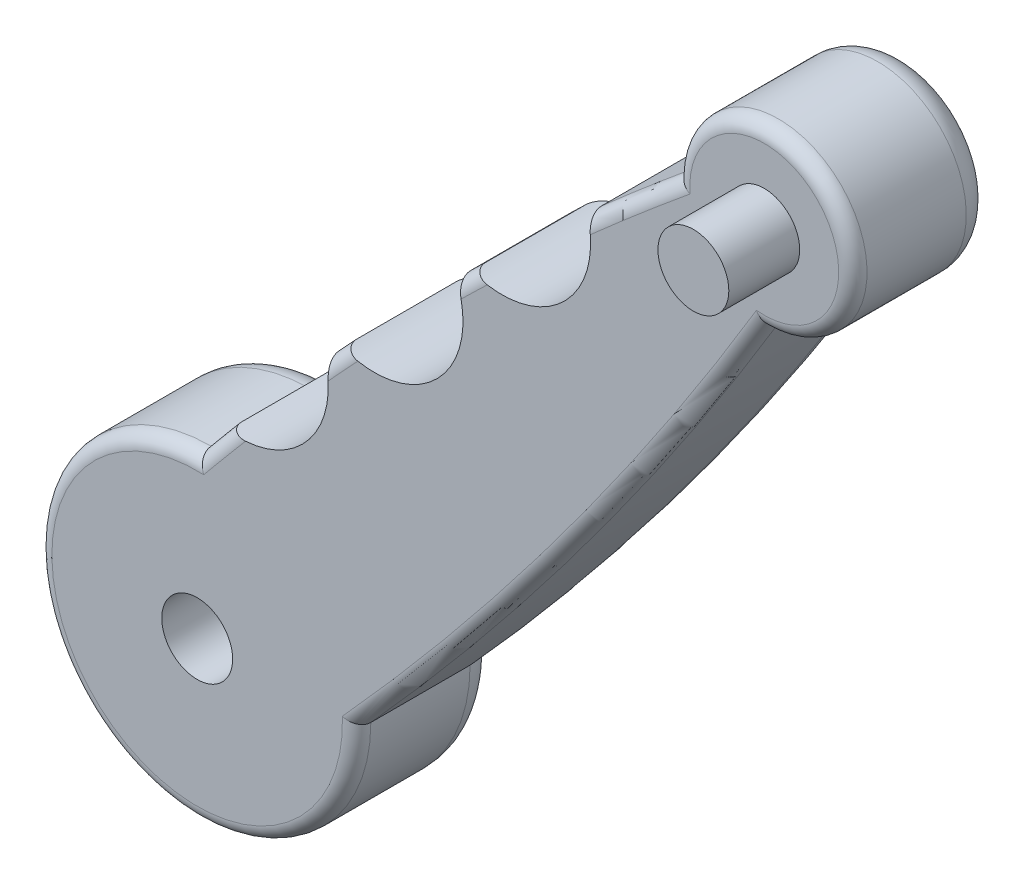
SolidWorks part; units mm, degrees
ref_plane "Front Plane" through (0, 0, 0) normal (0, 0, 1) x (1, 0, 0)
ref_plane "Top Plane" through (0, 0, 0) normal (0, 1, 0) x (1, 0, 0)
ref_plane "Right Plane" through (0, 0, 0) normal (1, 0, 0) x (0, 0, -1)
sketch "Sketch1" plane through (0, 0, 0) normal (0, 0, 1) x (1, 0, 0)
  arc A0 (0, 22.5) -> (22.5, 0) centre (0, 0) ccw
  arc A1 (80, 77.5) -> (67.5, 90) centre (80, 90) ccw
  arc A2 (0, 22.5) -> (67.5, 90) centre (385.6888, -295.6888) cw
  arc A3 (22.5, 0) -> (80, 77.5) centre (-348.4249, 335.283) ccw
  dimension "D1" = 45
  dimension "D2" = 25
  dimension "D3" = 90
  dimension "D5" = 500
  dimension "D6" = 500
  dimension "D4" = 80
extrude "Boss-Extrude1" add sketch "Sketch1" along normal mid plane 20 contours A2 A1 A3 A0
fillet "Fillet1" radius 2 4 edges at (53.1241, 37.3595, 10) (88.8388, 98.8388, 10) (32.1354, 57.8646, 10) (-15.9099, -15.9099, 10)
sketch "Sketch2" plane through (0, 0, 10) normal (0, 0, 1) x (1, 0, 0)
  circle A0 centre (0, 0) radius 5
  circle A1 centre (80, 90) radius 5
  dimension "D1" = 10
  dimension "D2" = 10
extrude "Boss-Extrude2" add sketch "Sketch2" along normal blind 10 contours A1
extrude "Cut-Extrude1" cut sketch "Sketch2<3>" against normal blind 10 contours A0
sketch "Sketch2<3>" plane through (0, 0, 10) normal (0, 0, 1) x (1, 0, 0) same geometry as "Sketch2"
fillet "Fillet2" radius 4 4 edges at (-15.9099, -15.9099, -10) (32.1354, 57.8646, -10) (53.1241, 37.3595, -10) (88.8388, 98.8388, -10)
sketch "Sketch3" plane through (0, 0, -10) normal (0, 0, -1) x (-1, 0, 0)
  circle A0 centre (0, 0) radius 12.5
  dimension "D1" = 25
extrude "Boss-Extrude3" add sketch "Sketch3" along normal blind 5
fillet "Fillet3" radius 5 1 edges at (-12.5, 0, -15)
sketch "Sketch4" plane through (0, 0, -15) normal (0, 0, -1) x (-1, 0, 0)
  line L0 (0, 0) -> (0, 12.5) construction
  circle A0 centre (0, 0) radius 12.5 construction
  circle A1 centre (0, 12.5) radius 2.5
  dimension "D1" = 5
extrude "Cut-Extrude2" cut sketch "Sketch4" against normal up to surface (5 mm away) up to face at (12.5, 0, -10)
pattern_circular "CirPattern1" count 8 over 360 about axis through (0, 0, -15) along (0, 0, -1) of "Cut-Extrude2"
sketch "Sketch5" plane through (0, 0, -10) normal (0, 0, -1) x (-1, 0, 0)
  circle A0 centre (0, 12.5) radius 1.75
  dimension "D1" = 3.5
extrude "Boss-Extrude4" add sketch "Sketch5" along normal blind 2
fillet "Fillet4" radius 1 1 edges at (-1.75, 12.5, -12)
pattern_circular "CirPattern2" count 8 over 360 about axis through (0, 0, -15) along (0, 0, -1) of "Fillet4", "Boss-Extrude4"
sketch "Sketch7" plane through (0, 0, -10) normal (0, 0, -1) x (-1, 0, 0)
  circle A4 centre (-80, 90) radius 5
  dimension "D5" = 10
extrude "Cut-Extrude3" cut sketch "Sketch7" against normal blind 2
sketch "Sketch9" plane through (0, 0, -10) normal (0, 0, -1) x (-1, 0, 0)
  arc A9 (-4.1388, 16.5108) -> (-73.5798, 85.9352) centre (-385.6888, -295.6888) ccw
  arc A10 (-11.8114, 25.6594) -> (-55.8988, 70.7638) centre (-385.6888, -295.6888) ccw
  arc A11 (-55.8988, 70.7638) -> (-63.4205, 64.299) centre (-59.2436, 67.0473) ccw
  arc A12 (-75.3122, 83.2992) -> (-16.2219, 3.4974) centre (348.4249, 335.283) ccw
  arc A13 (-63.4205, 64.299) -> (-25.4525, 13.9348) centre (348.4249, 335.283) ccw
  arc A14 (-25.4525, 13.9348) -> (-11.8114, 25.6594) centre (-18.6319, 19.7971) ccw
  dimension "D3" = 10
  dimension "D4" = 17.9874
  dimension "D1" = 3
  dimension "D2" = 3
extrude "Cut-Extrude4" cut sketch "Sketch9" against normal blind 2 contours A13 A14 A10 A11
sketch "Sketch11" plane through (0, 0, 0) normal (0, 0, 1) x (1, 0, 0)
  circle A0 centre (43, 76) radius 12.5
  circle A1 centre (25, 57.5) radius 12.5
  circle A2 centre (6, 40) radius 12.5
  dimension "D1" = 25
  dimension "D2" = 76
  dimension "D3" = 43
  dimension "D4" = 57.5
  dimension "D5" = 25
  dimension "D6" = 40
  dimension "D7" = 6
extrude "Cut-Extrude5" cut sketch "Sketch11" against normal through all both and the other way through all
